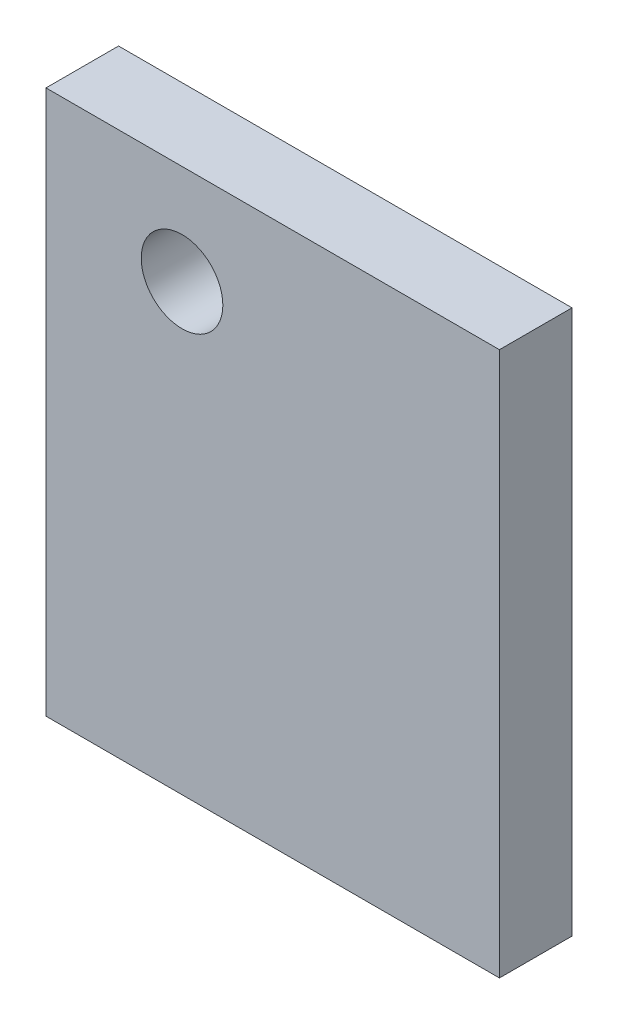
SolidWorks part; units mm, degrees
ref_plane "Front Plane" through (0, 0, 0) normal (0, 0, 1) x (1, 0, 0)
ref_plane "Top Plane" through (0, 0, 0) normal (0, 1, 0) x (1, 0, 0)
ref_plane "Right Plane" through (0, 0, 0) normal (1, 0, 0) x (0, 0, -1)
sketch "Sketch1" plane through (0, 0, 0) normal (0, 0, 1) x (1, 0, 0)
  line L1 (-25, -30) -> (25, -30)
  line L2 (-25, -30) -> (-25, 30)
  line L3 (-25, 30) -> (25, 30)
  line L4 (25, -30) -> (25, 30)
  line L5 (-25, -30) -> (25, 30) construction
  line L6 (-25, 30) -> (25, -30) construction
  circle A0 centre (-10, 19) radius 4.5
  point P0 (0, 0)
  dimension "D3" = 11
  dimension "D5" = 9
  dimension "D1" = 60
  dimension "D2" = 50
  dimension "D4" = 15
extrude "Boss-Extrude1" add sketch "Sketch1" along normal blind 8
